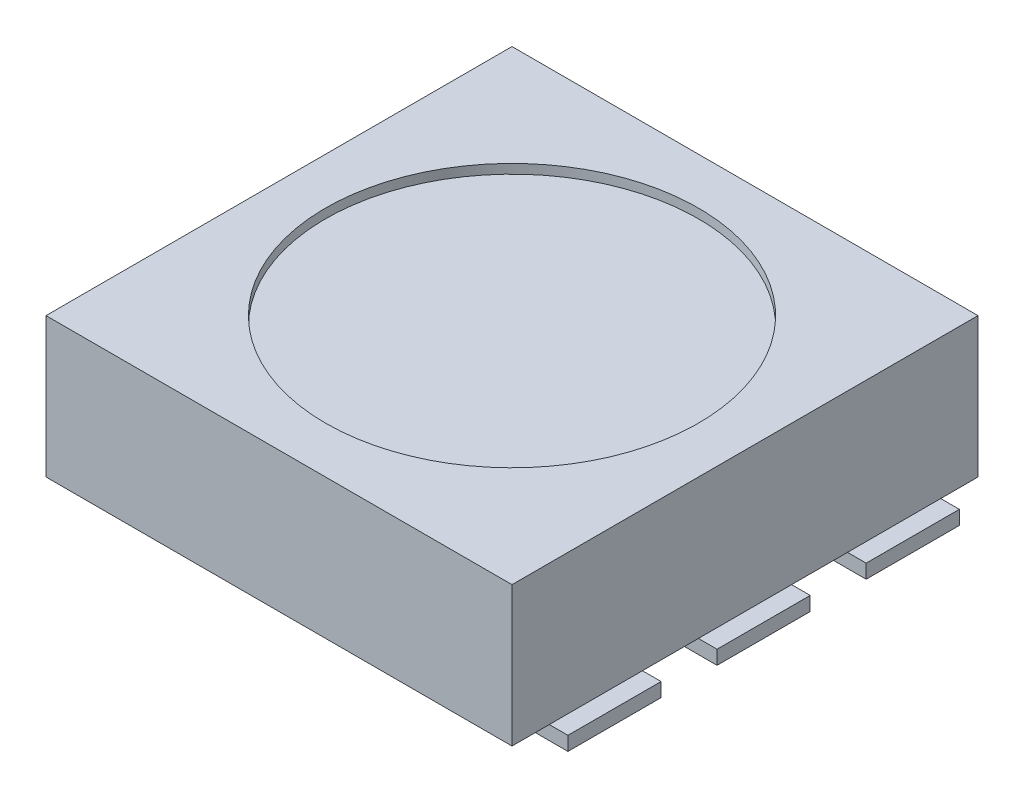
SolidWorks part; units mm, degrees
ref_plane "Front Plane" through (0, 0, 0) normal (0, 0, 1) x (1, 0, 0)
ref_plane "Top Plane" through (0, 0, 0) normal (0, 1, 0) x (1, 0, 0)
ref_plane "Right Plane" through (0, 0, 0) normal (1, 0, 0) x (0, 0, -1)
sketch "Sketch1" plane through (0, 0, 0) normal (0, 1, 0) x (1, 0, 0)
  line L0 (1.7, -2.1) -> (1.7, -1.1)
  line L1 (-2.5, 2.5) -> (2.5, 2.5)
  line L2 (-2.5, 2.5) -> (-2.5, -2.5)
  line L3 (-2.5, -2.5) -> (2.5, -2.5)
  line L4 (2.5, 2.5) -> (2.5, -2.5)
  line L5 (-2.5, 2.5) -> (2.5, -2.5) construction
  line L6 (-2.5, -2.5) -> (2.5, 2.5) construction
  line L7 (-2.7, -2.1) -> (-1.7, -2.1)
  line L8 (-2.7, -2.1) -> (-2.7, -1.1)
  line L9 (-2.7, -1.1) -> (-1.7, -1.1)
  line L10 (-1.7, -2.1) -> (-1.7, -1.1)
  line L11 (-2.7, -2.1) -> (-1.7, -1.1) construction
  line L12 (-2.7, -1.1) -> (-1.7, -2.1) construction
  line L13 (1.7, -2.1) -> (2.7, -2.1)
  line L14 (2.7, -2.1) -> (2.7, -1.1)
  line L15 (1.7, -1.1) -> (2.7, -1.1)
  line L16 (1.7, -0.5) -> (1.7, 0.5)
  line L17 (1.7, -0.5) -> (2.7, -0.5)
  line L18 (2.7, -0.5) -> (2.7, 0.5)
  line L19 (1.7, 0.5) -> (2.7, 0.5)
  line L20 (1.7, 1.1) -> (1.7, 2.1)
  line L21 (1.7, 1.1) -> (2.7, 1.1)
  line L22 (2.7, 1.1) -> (2.7, 2.1)
  line L23 (1.7, 2.1) -> (2.7, 2.1)
  line L24 (-2.7, -0.5) -> (-2.7, 0.5)
  line L25 (-2.7, -0.5) -> (-1.7, -0.5)
  line L26 (-1.7, -0.5) -> (-1.7, 0.5)
  line L27 (-2.7, 0.5) -> (-1.7, 0.5)
  line L28 (-2.7, 1.1) -> (-2.7, 2.1)
  line L29 (-2.7, 1.1) -> (-1.7, 1.1)
  line L30 (-1.7, 1.1) -> (-1.7, 2.1)
  line L31 (-2.7, 2.1) -> (-1.7, 2.1)
  line L32 (-1.7, -2.1) -> (1.7, -2.1) construction
  point P0 (0, 0)
  point P6 (-2.2, -1.6)
  point P12 (0, -2.1)
  point P13 (-1.7, 0)
  point P33 (-2.1802, -0.5)
  point P34 (2.7, -1.9309)
  point P35 (-1.7, -1.6)
  dimension "D1" = 5
  dimension "D4" = 3.4
  dimension "D5" = 1
  dimension "D6" = 5.4
  dimension "D7" = 1.6
  dimension "D2" = 2
  dimension "D3" = 3
extrude "Boss-Extrude1" add sketch "Sketch1" along normal blind 1.5 contours L3 L4 L1 L2
extrude "Boss-Extrude2" add sketch "Sketch1<3>" against normal blind 0.15 contours L8 L9 L10 L7 | L24 L27 L26 L25 | L28 L31 L30 L29 | L14 L15 L0 L13 | L18 L19 L16 L17 | L22 L23 L20 L21
sketch "Sketch1<3>" plane through (0, 0, 0) normal (0, 1, 0) x (1, 0, 0) same geometry as "Sketch1"
sketch "Sketch2" plane through (0, 1.5, 0) normal (0, 1, 0) x (1, 0, 0)
  circle A0 centre (0, 0) radius 2
  dimension "D1" = 4
extrude "Cut-Extrude1" cut sketch "Sketch2" against normal blind 0.1
